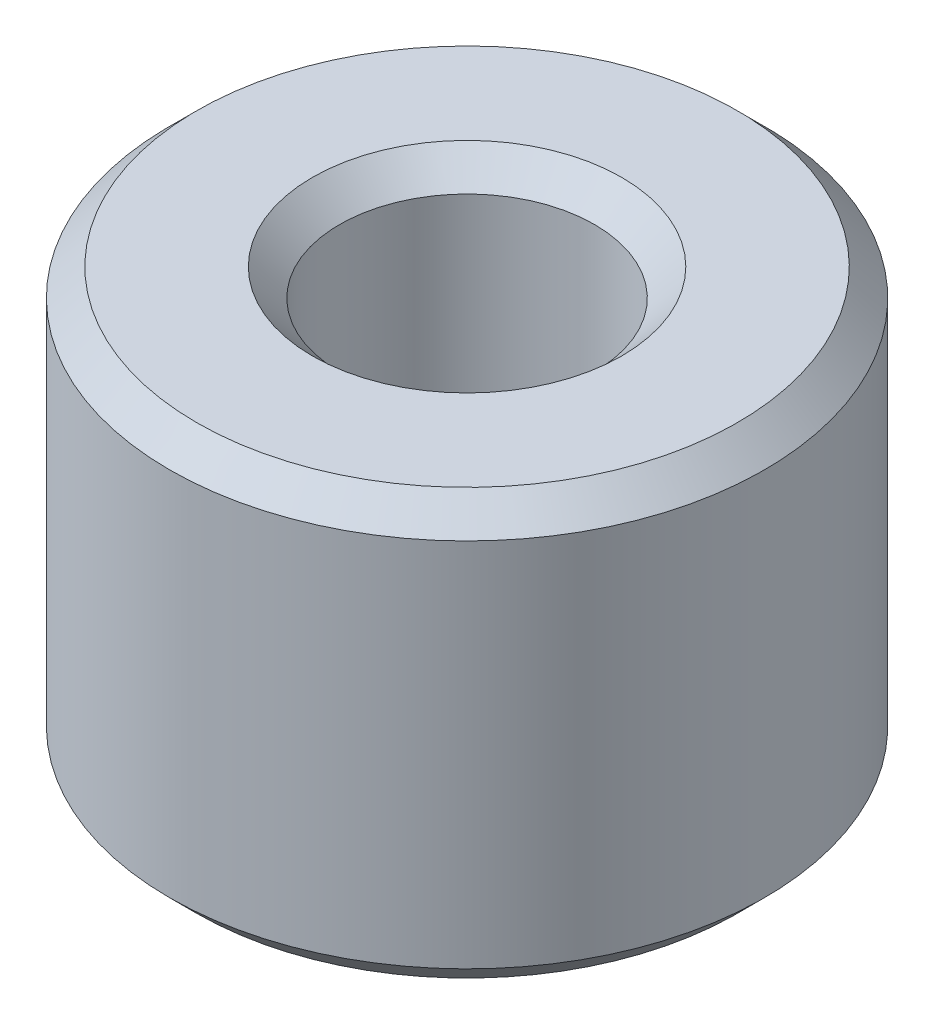
SolidWorks part; units mm, degrees
material "2024-T4"
ref_plane "Front Plane" through (0, 0, 0) normal (0, 0, 1) x (1, 0, 0)
ref_plane "Top Plane" through (0, 0, 0) normal (0, 1, 0) x (1, 0, 0)
ref_plane "Right Plane" through (0, 0, 0) normal (1, 0, 0) x (0, 0, -1)
sketch "Sketch1" plane through (0, 0, 0) normal (0, 1, 0) x (1, 0, 0)
  circle A0 centre (0, 0) radius 5.5562
  circle A1 centre (0, 0) radius 2.3812
  dimension "D1" = 4.7625
  dimension "D2" = 11.1125
extrude "Boss-Extrude1" add sketch "Sketch1" along normal blind 7.9375
chamfer "Chamfer1" distance 0.508 angle 45 4 edges at (0, 0, 2.3812) (0, 0, 5.5562) (0, 7.9375, 2.3812) (0, 7.9375, 5.5562)
